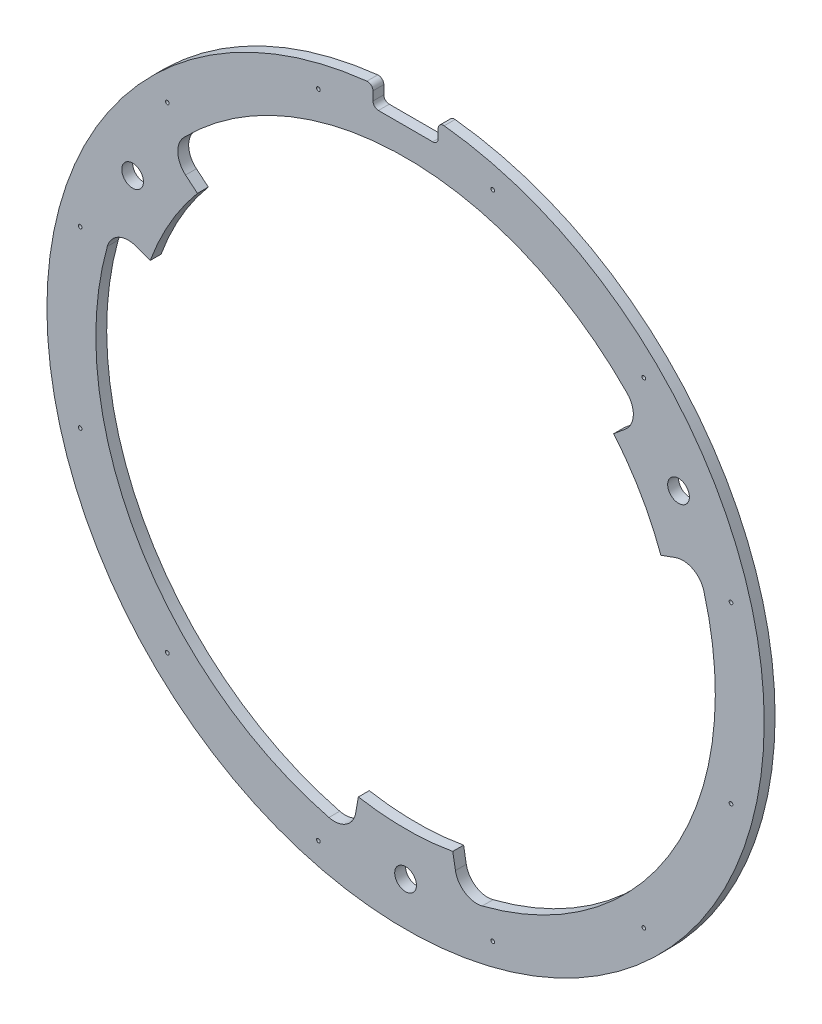
SolidWorks part; units mm, degrees
ref_plane "Front Plane" through (0, 0, 0) normal (0, 0, 1) x (1, 0, 0)
ref_plane "Top Plane" through (0, 0, 0) normal (0, 1, 0) x (1, 0, 0)
ref_plane "Right Plane" through (0, 0, 0) normal (1, 0, 0) x (0, 0, -1)
sketch "Sketch2" plane through (0, 0, 0) normal (0, 0, 1) x (1, 0, 0)
  circle A0 centre (0, 0) radius 330
  circle A2 centre (0, 0) radius 250
  dimension "D1" = 660
  dimension "D2" = 500
extrude "Boss-Extrude1" add sketch "Sketch2" along normal blind 10
sketch "Sketch3" plane through (0, 0, 10) normal (0, 0, 1) x (1, 0, 0)
  line L0 (191.5111, 160.6969) -> (202.4228, 169.8529)
  line L1 (-191.5111, 160.6969) -> (-202.4228, 169.8529)
  line L2 (43.412, -246.2019) -> (45.8855, -260.2297)
  line L4 (234.9232, 85.505) -> (248.3083, 90.3768)
  line L6 (0, 0) -> (0, 240.4153) construction
  line L7 (191.5111, 160.6969) -> (0, 0) construction
  line L8 (-234.9232, 85.505) -> (-248.3083, 90.3768)
  line L9 (-43.412, -246.2019) -> (-45.8855, -260.2297)
  arc A0 (203.874, 199.1492) -> (-203.874, 199.1492) centre (0, 0) ccw
  circle A1 centre (0, 0) radius 250 construction
  arc A2 (191.5111, 160.6969) -> (-191.5111, 160.6969) centre (0, 0) ccw
  arc A3 (-202.4228, 169.8529) -> (-203.874, 199.1492) centre (-189.5671, 185.1738) cw
  arc A4 (202.4228, 169.8529) -> (203.874, 199.1492) centre (189.5671, 185.1738) ccw
  circle A5 centre (0, 0) radius 330 construction
  arc A6 (70.5312, -276.1346) -> (274.4052, 76.9855) centre (0, 0) ccw
  arc A7 (43.412, -246.2019) -> (234.9232, 85.505) centre (0, 0) ccw
  arc A8 (248.3083, 90.3768) -> (274.4052, 76.9855) centre (255.1487, 71.583) cw
  arc A9 (45.8855, -260.2297) -> (70.5312, -276.1346) centre (65.5817, -256.7568) ccw
  arc A10 (-274.4052, 76.9855) -> (-70.5312, -276.1346) centre (0, 0) ccw
  arc A11 (-234.9232, 85.505) -> (-43.412, -246.2019) centre (0, 0) ccw
  arc A12 (-45.8855, -260.2297) -> (-70.5312, -276.1346) centre (-65.5817, -256.7568) cw
  arc A13 (-248.3083, 90.3768) -> (-274.4052, 76.9855) centre (-255.1487, 71.583) ccw
  point P33 (0, 0)
  dimension "D1" = 45
  dimension "D3" = 20
  dimension "D2" = 100
  dimension "D4" = 3
extrude "Cut-Extrude1" cut sketch "Sketch3" against normal blind 10
sketch "Sketch4" plane through (0, 0, 10) normal (0, 0, 1) x (1, 0, 0)
  line L0 (0, 0) -> (0, -290) construction
  circle A0 centre (0, -290) radius 10
  circle A1 centre (-251.1474, 145) radius 10
  circle A2 centre (251.1474, 145) radius 10
  point P11 (0, 0)
  dimension "D1" = 20
  dimension "D2" = 290
  dimension "D3" = 3
extrude "Cut-Extrude2" cut sketch "Sketch4" against normal blind 10
sketch "Sketch5" plane through (0, 0, 10) normal (0, 0, 1) x (1, 0, 0)
  line L0 (0, 0) -> (0, 370) construction
  line L1 (30, 370) -> (30, 310)
  line L2 (30, 370) -> (-30, 370)
  line L4 (30, 310) -> (-30, 310)
  line L5 (-30, 370) -> (-30, 310)
  dimension "D1" = 310
  dimension "D2" = 60
  dimension "D3" = 60
extrude "Cut-Extrude3" cut sketch "Sketch5" against normal blind 10
fillet "Fillet1" radius 5 4 edges at (30, 328.6335, 5) (-30, 328.6335, 5) (30, 310, 5) (-30, 310, 5)
hole_wizard "CSK for M3 Flat Head Machine Screw1" positions "Sketch6" profile "Sketch7" countersink size "M3" standard "ANSI Metric" end condition through all
sketch "Sketch6" plane through (0, 0, -20) normal (0, 0, -1) x (1, 0, 0)
  line L0 (80.2339, 299.437) -> (0, 0) construction
  line L2 (0, 0) -> (0, 423.7069) construction
  circle A0 centre (0, 0) radius 310 construction
  point P0 (80.2339, 299.437)
  point P21 (219.2031, 219.2031)
  point P22 (299.437, 80.2339)
  point P23 (299.437, -80.2339)
  point P24 (219.2031, -219.2031)
  point P25 (80.2339, -299.437)
  point P26 (-80.2339, -299.437)
  point P27 (-219.2031, -219.2031)
  point P28 (-299.437, -80.2339)
  point P29 (-299.437, 80.2339)
  point P30 (-219.2031, 219.2031)
  point P31 (-80.2339, 299.437)
  point P32 (0, 0)
sketch "Sketch7" plane through (80.2339, -299.437, -20) normal (1, 0, 0) x (0, 1, 0)
  line L0 (0, 0) -> (0, 30)
  line L1 (0, 30) -> (1.7, 30)
  line L2 (1.7, 30) -> (1.7, 1.45)
  line L3 (1.7, 1.45) -> (3.15, 0)
  line L4 (3.15, 0) -> (0, 0)
  line L5 (-1.7, 1.45) -> (-3.15, 0) construction
  line L6 (0, -6.35) -> (0, 107.95) construction
  dimension "Thru Hole Dia." = 3.4
  dimension "Thru Hole Depth" = 30
  dimension "Near C'Sink Dia." = 6.3
  dimension "Near C'Sink Angle" = 90
